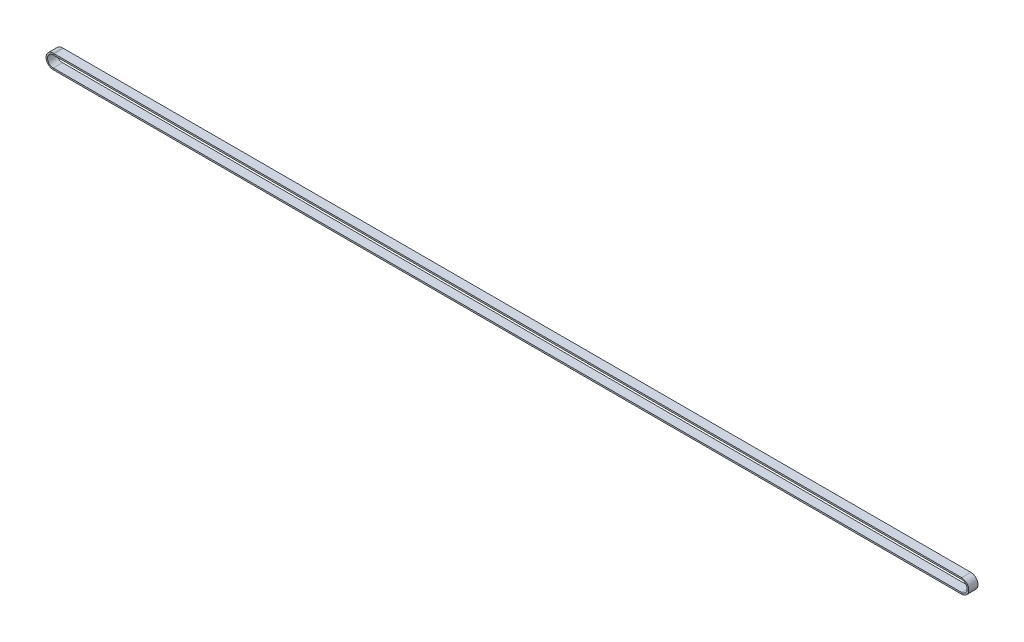
SolidWorks part; units mm, degrees
ref_plane "Front Plane" through (0, 0, 0) normal (0, 0, 1) x (1, 0, 0)
ref_plane "Top Plane" through (0, 0, 0) normal (0, 1, 0) x (1, 0, 0)
ref_plane "Right Plane" through (0, 0, 0) normal (1, 0, 0) x (0, 0, -1)
sketch "Sketch2" plane through (0, 0, 0) normal (0, 0, 1) x (1, 0, 0)
  line L0 (0, 0) -> (1, 0) construction
  line L1 (0, 0) -> (0, 1) construction
  line L2 (-1, -68.182) -> (883.5206, -68.182)
  line L3 (883.5206, -82.182) -> (-1, -82.182)
  arc A0 (-1, -82.182) -> (-1, -68.182) centre (-1, -75.182) cw
  arc A1 (883.5206, -68.182) -> (883.5206, -82.182) centre (883.5206, -75.182) cw
sketch "Sketch3" plane through (0, 0, 0) normal (1, 0, 0) x (0, 0, -1)
  line L1 (0, -69.682) -> (-9, -69.682)
  line L2 (0, -69.682) -> (0, -68.182)
  line L3 (0, -68.182) -> (-9, -68.182)
  line L4 (-9, -69.682) -> (-9, -68.182)
  dimension "D1" = 9
  dimension "D2" = 1.5
sweep "Sweep1" add profiles "Sketch3" path "Sketch2"
